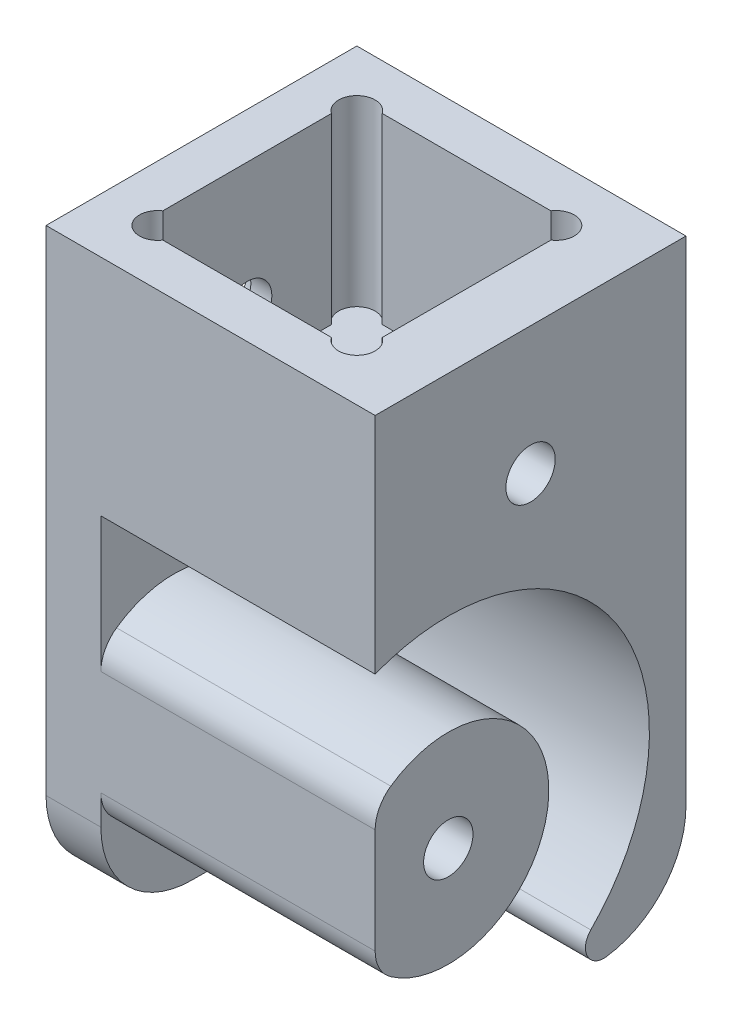
SolidWorks part; units mm, degrees
material "6061-T6 (SS)"
ref_plane "前视基准面" through (0, 0, 0) normal (0, 0, 1) x (1, 0, 0)
ref_plane "上视基准面" through (0, 0, 0) normal (0, 1, 0) x (1, 0, 0)
ref_plane "右视基准面" through (0, 0, 0) normal (1, 0, 0) x (0, 0, -1)
sketch "草图1" plane through (0, 0, 0) normal (0, 1, 0) x (1, 0, 0)
  line L0 (-6.5, -6) -> (-6.5, 6)
  line L1 (-9, -8.5) -> (9, -8.5)
  line L2 (-9, -8.5) -> (-9, 8.5)
  line L3 (-9, 8.5) -> (9, 8.5)
  line L4 (9, -8.5) -> (9, 8.5)
  line L5 (0, 8.5) -> (0, -8.5) construction
  line L6 (-9, 0) -> (9, 0) construction
  line L7 (-6.5, 6) -> (5.5, 6)
  line L8 (5.5, -6) -> (5.5, 6)
  line L9 (-6.5, -6) -> (5.5, -6)
  line L10 (-6.5, 6) -> (5.5, -6) construction
  line L11 (5.5, 6) -> (-6.5, -6) construction
  point P0 (0, 0)
  point P8 (-0.5, 0)
  dimension "D1" = 18
  dimension "D2" = 12
  dimension "D3" = 17
  dimension "D4" = 8.5
extrude "凸台-拉伸1" add sketch "草图1" along normal blind 10
sketch "草图4" plane through (0, 0, 0) normal (0, -1, 0) x (1, 0, 0)
  line L1 (9, -8.5) -> (9, 8.5)
  line L2 (9, 8.5) -> (-9, 8.5)
  line L3 (-9, 8.5) -> (-9, -8.5)
  line L4 (-9, -8.5) -> (9, -8.5)
  line L5 (9, -8.5) -> (9, 8.5)
  line L6 (9, 8.5) -> (-9, 8.5)
  line L7 (-9, 8.5) -> (-9, -8.5)
  line L12 (-9, -8.5) -> (9, -8.5)
  line L13 (9, -8.5) -> (9, 8.5) construction
  line L14 (9, 8.5) -> (-9, 8.5) construction
  line L15 (-9, 8.5) -> (-9, -8.5) construction
  line L16 (-9, -8.5) -> (9, -8.5) construction
  dimension "D1" = 0
  dimension "D2" = 0
extrude "凸台-拉伸2" add sketch "草图4" along normal blind 22
sketch "草图5" plane through (9, 0, 0) normal (-1, 0, 0) x (0, 0, 1)
  line L0 (0, 0) -> (0, -22) construction
  line L1 (8.5, 10) -> (-8.5, 10) construction
  line L2 (4.5, -12.5) -> (0, -12.5) construction
  line L3 (-8.5, -22) -> (8.5, -22) construction
  circle A0 centre (4.5, -12.5) radius 11
  dimension "D1" = 22
  dimension "D2" = 4.5
  dimension "D3" = 22.5
extrude "切除-拉伸1" cut sketch "草图5" along normal offset from surface (15 mm away) 3 up to face at (-9, -6, 0)
sketch "草图8" plane through (-6, 0, 0) normal (1, 0, 0) x (0, 0, -1)
  line L0 (-8.5, -2.253) -> (-8.5, -22) construction
  arc A1 (-8.5, -16.2749) -> (-8.5, -8.7251) centre (-4.5, -12.5) ccw
  circle A2 centre (-4.5, -12.5) radius 1.25
  arc A3 (1.0453, -22) -> (-8.5, -2.253) centre (-4.5, -12.5) ccw construction
  dimension "D1" = 11
  dimension "D2" = 2.5
extrude "凸台-拉伸3" add sketch "草图8" along normal up to surface (15 mm away)
sketch "草图13" plane through (9, 0, 0) normal (1, 0, 0) x (0, 0, -1)
  line L0 (0, 0) -> (0, 10) construction
  line L1 (-8.5, 10) -> (8.5, 10) construction
  circle A0 centre (0, 3) radius 1.25
  dimension "D2" = 2.5
  dimension "D1" = 7
extrude "切除-拉伸5" cut sketch "草图13" against normal through all
sketch "草图9" plane through (9, 0, 0) normal (1, 0, 0) x (0, 0, -1)
  circle A0 centre (-4.5, -12.5) radius 1.35
extrude "切除-拉伸3" cut sketch "草图9" against normal through all
sketch "草图20" plane through (0, 10, 0) normal (0, 1, 0) x (1, 0, 0)
  line L0 (5.5, 6) -> (-6.5, -6) construction
  line L1 (5.6518, -6.1518) -> (-6.5, 6) construction
  line L2 (-0.5, 6) -> (-0.5, 0) construction
  line L3 (5.5, 6) -> (-6.5, 6) construction
  line L4 (-0.5, 0) -> (-6.5, 0) construction
  line L5 (-6.5, 6) -> (-6.5, -6) construction
  circle A0 centre (4.9447, -5.4447) radius 1
  circle A1 centre (4.9447, 5.4447) radius 1
  circle A2 centre (-5.9447, 5.4447) radius 1
  circle A3 centre (-5.9447, -5.4447) radius 1
  dimension "D1" = 2
  dimension "D2" = 7.7
fillet "圆角4" radius 5 1 edges at (0, -22, -8.5)
extrude "切除-拉伸7" cut sketch "草图20" against normal up to surface (10 mm away) up to face at (-0.5, 0, 0)
fillet "圆角5" radius 5 1 edges at (-7.5, -22, 8.5)
fillet "圆角6" radius 2 2 edges at (1.5, -8.7251, 8.5) (1.5, -16.2749, 8.5)
fillet "圆角7" radius 1 1 edges at (1.5, -22, -1.0453)
hole_wizard "打孔尺寸(%根据十字)槽沉头木螺钉的类型1" positions "草图21" profile "草图22" countersink size "M2.5" standard "GB" end condition through all
sketch "草图21" plane through (-9, 0, 0) normal (-1, 0, 0) x (0, 0, 1)
  circle A0 centre (4.5, -12.5) radius 1.35 construction
  point P0 (4.5, -12.5)
  point P3 (0, 3)
sketch "草图22" plane through (-9, -12.5, 4.5) normal (0, 1, 0) x (0, 0, 1)
  line L0 (0, 0) -> (0, 18)
  line L1 (0, 18) -> (1.35, 18)
  line L2 (1.35, 18) -> (1.35, 1.35)
  line L3 (1.35, 1.35) -> (2.7, 0)
  line L5 (2.7, 0) -> (0, 0)
  line L6 (-1.35, 1.35) -> (-2.7, 0) construction
  line L11 (0, -6.35) -> (0, 107.95) construction
  dimension "通孔孔直径" = 2.7
  dimension "通孔孔深度" = 18
  dimension "近端锥形沉头孔直径" = 5.4
  dimension "近端锥形沉头孔角度" = 90
